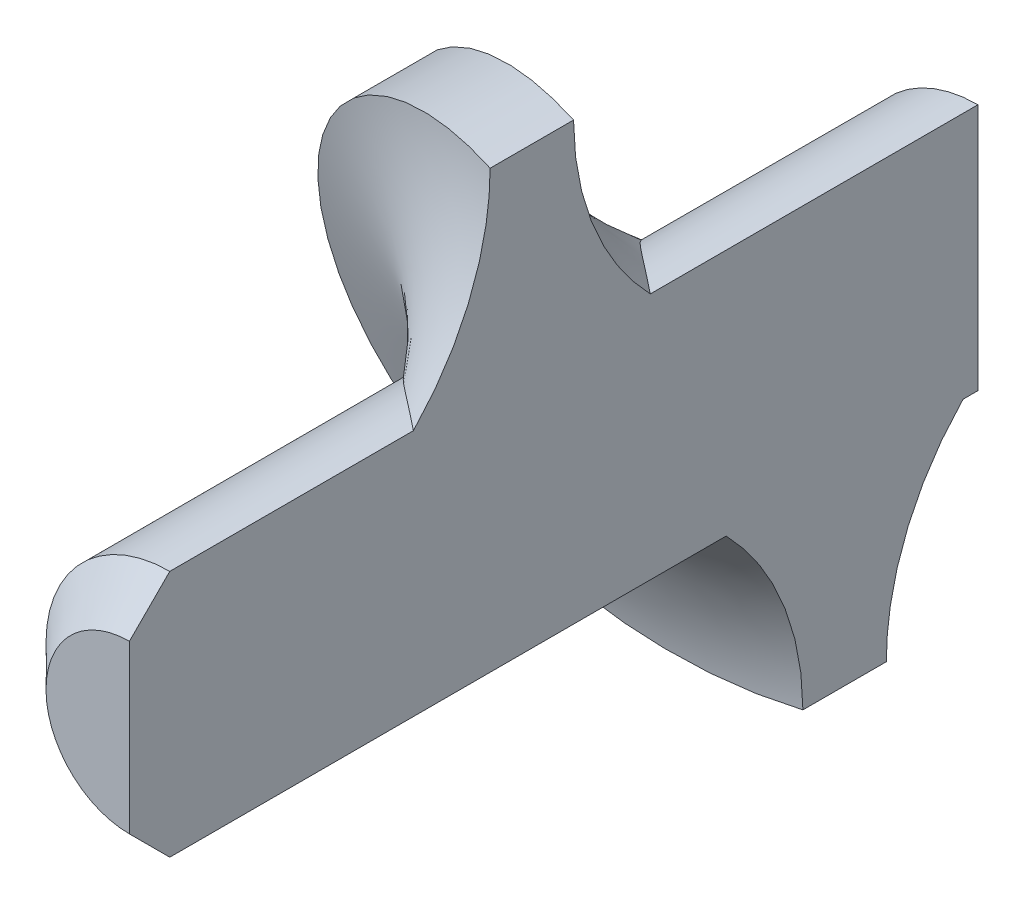
SolidWorks part; units mm, degrees
ref_plane "Plano frontal" through (0, 0, 0) normal (0, 0, 1) x (1, 0, 0)
ref_plane "Plano superior" through (0, 0, 0) normal (0, 1, 0) x (1, 0, 0)
ref_plane "Plano direito" through (0, 0, 0) normal (1, 0, 0) x (0, 0, -1)
sketch "Esboço1" plane through (0, 0, 0) normal (0, 0, 1) x (1, 0, 0)
  circle A0 centre (0, 0) radius 38.1
  dimension "D1" = 76.2
curve "Hélice/Espiral1" pitch 76.2 height 609.6 radius 38.1 left hand yes centre (0, 0, 0) axis (0, 0, 1) start towards (1, 0, 0)
extrude "Ressalto-extrusão1" add sketch "Esboço1<2>" along normal blind 533.4
sketch "Esboço1<2>" plane through (0, 0, 0) normal (0, 0, 1) x (1, 0, 0) same geometry as "Esboço1"
sketch "Esboço2" plane through (0, 0, 0) normal (0, 1, 0) x (1, 0, 0)
  line L2 (0, 0) -> (-38.1, 0) construction
  circle A0 centre (-38.1, 0) radius 33.02
  point P2 (-121.4222, -443.7967)
  point P3 (0, 0)
  point P4 (-102.7231, -30.4168)
  point P5 (0, 0)
  dimension "D1" = 66.04
sweep "Varredura de corte1" cut profiles "Esboço2" path "Hélice/Espiral1" align with end faces yes
sketch "Esboço5" plane through (0, 0, 0) normal (0, 0, 1) x (1, 0, 0)
  circle A0 centre (0, 0) radius 15.0813
  dimension "D1" = 30.1625
extrude "Ressalto-extrusão2" add sketch "Esboço5" along normal blind 563.372 and the other way blind 23
sketch "Esboço6" plane through (0, 0, -23) normal (0, 0, -1) x (-1, 0, 0)
  circle A0 centre (0, 0) radius 30.4211
extrude "Ressalto-extrusão3" add sketch "Esboço6" along normal blind 17
sketch "Croquis1" plane through (0, 0, 0) normal (0, 0, -1) x (-1, 0, 0)
  circle A0 centre (0, 0) radius 38.1
  circle A1 centre (0, 0) radius 15.0812
  dimension "D1" = 76.2
extrude "Cortar-Extruir2" cut sketch "Croquis1" against normal blind 5.588
ref_plane "Plano1" through (2.54, 0, 0) normal (1, 0, 0) x (0, 0, -1)
chamfer "Chaflán1" distance 4.92 angle 45 1 edges at (15.0813, 0, 563.372)
sketch "Croquis3" plane through (0, 0, 563.372) normal (0, 0, 1) x (1, 0, 0)
  line L1 (0, -38.1) -> (42.5251, -38.1)
  line L2 (0, -38.1) -> (0, 40.8348)
  line L3 (0, 40.8348) -> (42.5251, 40.8348)
  line L4 (42.5251, -38.1) -> (42.5251, 40.8348)
  circle A0 centre (0, 0) radius 38.1 construction
extrude "Cortar-Extruir3" cut sketch "Croquis3" against normal through all
sketch "Croquis5" plane through (0, 0, -40) normal (0, 0, -1) x (-1, 0, 0)
  line L1 (38.1, -38.1) -> (-41.3229, -38.1)
  line L2 (38.1, -38.1) -> (38.1, 38.1)
  line L3 (38.1, 38.1) -> (-41.3229, 38.1)
  line L4 (-41.3229, -38.1) -> (-41.3229, 38.1)
extrude "Cortar-Extruir4" cut sketch "Croquis5" against normal blind 500
